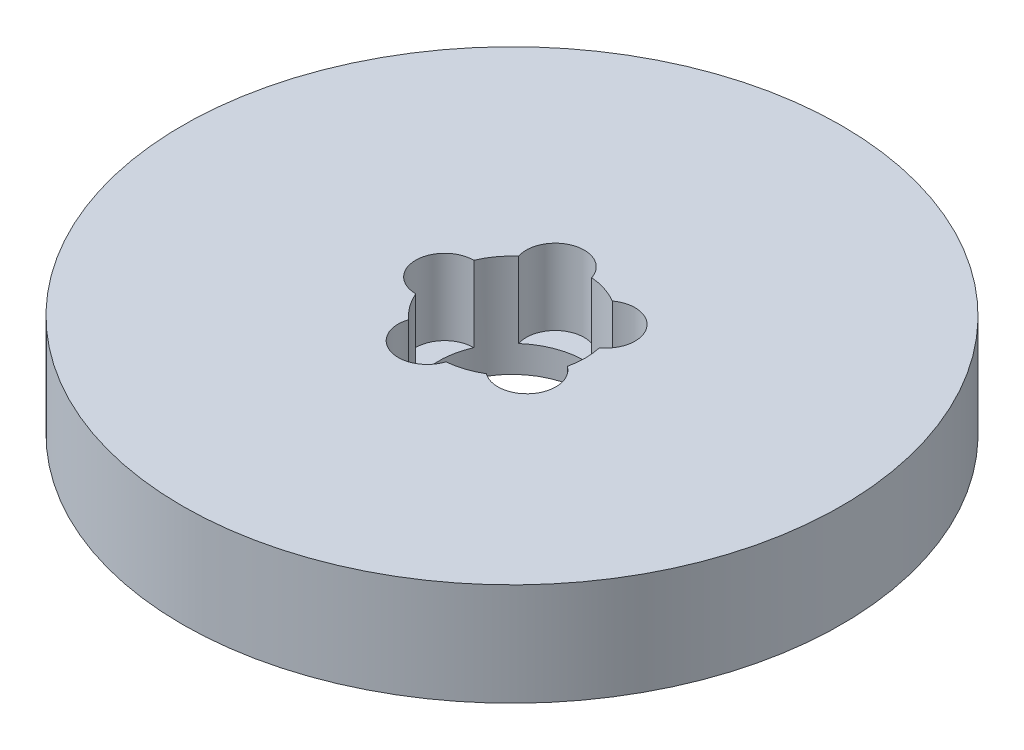
SolidWorks part; units mm, degrees
ref_plane "Front Plane" through (0, 0, 0) normal (0, 0, 1) x (1, 0, 0)
ref_plane "Top Plane" through (0, 0, 0) normal (0, 1, 0) x (1, 0, 0)
ref_plane "Right Plane" through (0, 0, 0) normal (1, 0, 0) x (0, 0, -1)
sketch "Sketch1" plane through (0, 0, 0) normal (0, 1, 0) x (1, 0, 0)
  circle A0 centre (0, 0) radius 22.5
  dimension "FLANGE_OD" = 45
extrude "Boss-Extrude1" add sketch "Sketch1" along normal blind 7
sketch "Sketch2" plane through (0, 0, 0) normal (0, 1, 0) x (1, 0, 0)
  circle A0 centre (0, 0) radius 5
  dimension "BORE_D" = 10
extrude "Cut-Extrude1" cut sketch "Sketch2" along normal through all
sketch "Sketch3" plane through (0, 7, 0) normal (0, 1, 0) x (1, 0, 0)
  circle A0 centre (0, 0) radius 4.5962 construction
  circle A1 centre (-4.5962, 0) radius 1.9814
  dimension "BOLT_D" = 3.9629
  dimension "BOLT_PCD" = 9.1925
extrude "Cut-Extrude2" cut sketch "Sketch3" against normal blind 5.1659
pattern_circular "CirPattern1" count 5 over 360 about axis through (0, 0, 0) along (0, 1, 0) of "Cut-Extrude2"
